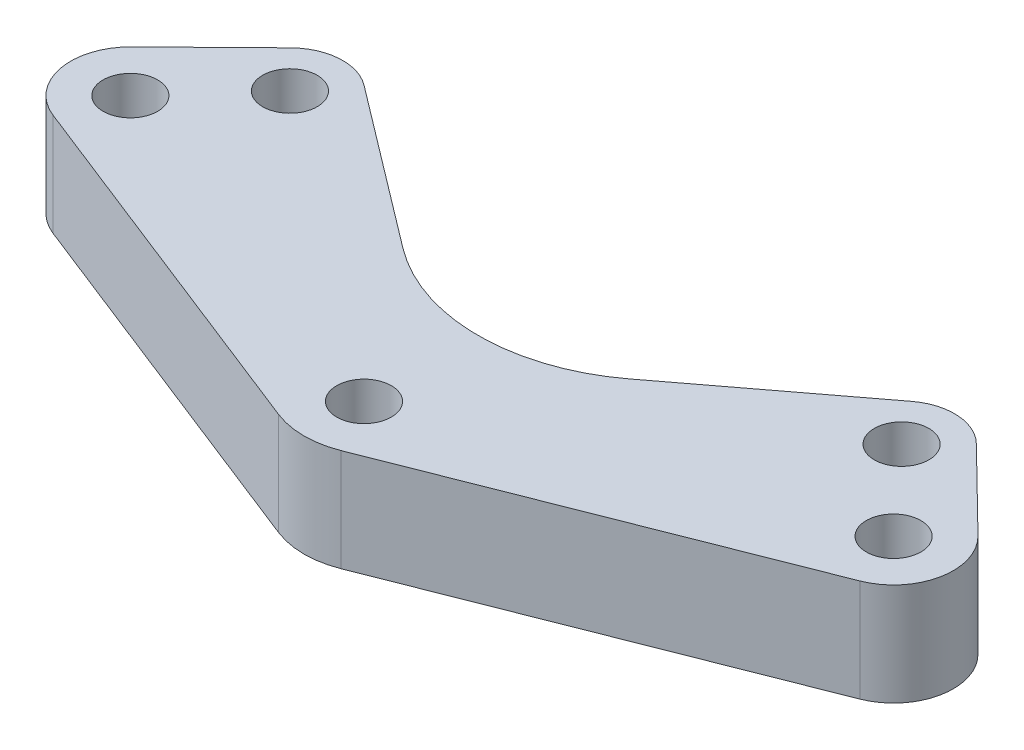
SolidWorks part; units mm, degrees
ref_plane "Plano frontal" through (0, 0, 0) normal (0, 0, 1) x (1, 0, 0)
ref_plane "Plano superior" through (0, 0, 0) normal (0, 1, 0) x (1, 0, 0)
ref_plane "Plano direito" through (0, 0, 0) normal (1, 0, 0) x (0, 0, -1)
ref_plane "Plano1" through (0, -6, 0) normal (0, -1, 0) x (1, 0, 0)
sketch "Esboço1" plane through (0, -6, 0) normal (0, -1, 0) x (1, 0, 0)
  line L0 (23.6582, -5.4198) -> (1.8308, 3.1692)
  line L1 (-1.8308, 3.1692) -> (-23.6582, -5.4198)
  line L2 (-24.8257, -11.1771) -> (-20.1015, -15.8044)
  line L3 (-16.06, -16.0604) -> (-6.6439, -8.9246)
  line L4 (6.6439, -8.9246) -> (16.06, -16.0604)
  line L5 (20.1015, -15.8044) -> (24.8257, -11.1771)
  line L6 (0, 0) -> (-22.3767, -8.6767) construction
  line L7 (0, 0) -> (22.3767, -8.6767) construction
  line L8 (-22.3767, -8.6767) -> (22.3767, -8.6767) construction
  line L9 (-17.9323, -13.5898) -> (17.9323, -13.5898) construction
  line L10 (17.9323, -13.5898) -> (0, 0) construction
  line L11 (0, 0) -> (-17.9323, -13.5898) construction
  arc A0 (1.8308, 3.1692) -> (-1.8308, 3.1692) centre (0, -1.4835) ccw
  arc A1 (-23.6582, -5.4198) -> (-24.8257, -11.1771) centre (-22.3767, -8.6767) ccw
  arc A2 (-20.1015, -15.8044) -> (-16.06, -16.0604) centre (-17.9323, -13.5898) ccw
  arc A3 (-6.6439, -8.9246) -> (6.6439, -8.9246) centre (0, -17.6915) cw
  arc A4 (16.06, -16.0604) -> (20.1015, -15.8044) centre (17.9323, -13.5898) ccw
  arc A5 (24.8257, -11.1771) -> (23.6582, -5.4198) centre (22.3767, -8.6767) ccw
  circle A6 centre (-17.9323, -13.5898) radius 1.6
  circle A7 centre (0, 0) radius 1.6
  circle A8 centre (17.9323, -13.5898) radius 1.6
  circle A9 centre (-22.3767, -8.6767) radius 1.6
  circle A10 centre (22.3767, -8.6767) radius 1.6
  point P24 (0, -13.5898)
  point P25 (0, -8.6767)
  point P26 (-62.936, -67.672)
  point P27 (0, 0)
  point P28 (-140.4705, -118.6622)
  point P29 (-131.0544, -111.7824)
  point P30 (-14.9536, -17.959)
  point P31 (0, 0)
  dimension "D1" = 3.2
  dimension "D2" = 24
  dimension "D4" = 3.5
  dimension "D9" = 11
  dimension "D12" = 3.5
  dimension "D13" = 3.6195
  dimension "D15" = 5
  dimension "D3" = 3.6195
  dimension "D5" = 137.612
  dimension "D6" = 105.688
  dimension "D7" = 22.5
  dimension "D8" = 3.1
  dimension "D11" = 17.6915
  dimension "D14" = 3.1
extrude "Ressalto-extrusão1" add sketch "Esboço1" against normal blind 6
